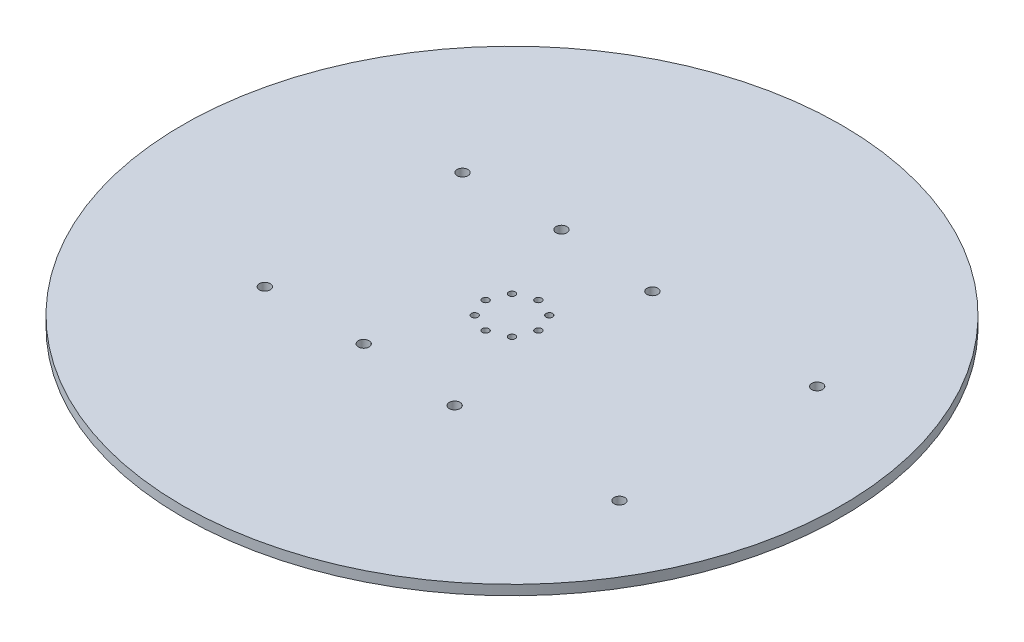
SolidWorks part; units mm, degrees
material "ABS"
ref_plane "Front Plane" through (0, 0, 0) normal (0, 0, 1) x (1, 0, 0)
ref_plane "Top Plane" through (0, 0, 0) normal (0, 1, 0) x (1, 0, 0)
ref_plane "Right Plane" through (0, 0, 0) normal (1, 0, 0) x (0, 0, -1)
sketch "Sketch2" plane through (0, 0, 0) normal (0, 1, 0) x (1, 0, 0)
  circle A0 centre (0, 0) radius 100
  dimension "D1" = 200
extrude "Boss-Extrude1" add sketch "Sketch2" along normal blind 3
sketch "Sketch3" plane through (0, 0, 0) normal (0, -1, 0) x (1, 0, 0)
  circle A0 centre (0, 75) radius 10
  dimension "D1" = 75
  dimension "D2" = 20
extrude "Boss-Extrude2" add sketch "Sketch3" along normal blind 4.75
sketch "Sketch4" plane through (0, 0, 0) normal (0, 0, 1) x (1, 0, 0)
  line L0 (0, 3) -> (0, -49997) construction
  line L1 (100, 3) -> (-100, 3) construction
  point P4 (0, 3)
pattern_circular "CirPattern1" count 5 over 360 about axis through (0, 3, 0) along (0, -1, 0) of "Boss-Extrude2"
fillet "Fillet3" radius 10 5 edges at (0, -4.75, 65) (61.8187, -4.75, 20.0861) (38.206, -4.75, -52.5861) (-38.206, -4.75, -52.5861) (-61.8187, -4.75, 20.0861)
sketch "Sketch5" plane through (0, 0, 0) normal (0, -1, 0) x (1, 0, 0)
  line L1 (-0.75, -9.5) -> (0.75, -9.5)
  line L2 (-0.75, -9.5) -> (-0.75, -12.5)
  line L3 (-0.75, -12.5) -> (0.75, -12.5)
  line L4 (0.75, -9.5) -> (0.75, -12.5)
  line L5 (-0.75, -9.5) -> (0.75, -12.5) construction
  line L6 (-0.75, -12.5) -> (0.75, -9.5) construction
  circle A0 centre (0, 0) radius 11
  circle A1 centre (0, 8) radius 1
  circle A2 centre (5.6569, 5.6569) radius 1
  circle A3 centre (8, 0) radius 1
  circle A4 centre (5.6569, -5.6569) radius 1
  circle A5 centre (0, -8) radius 1
  circle A6 centre (-5.6569, -5.6569) radius 1
  circle A7 centre (-8, 0) radius 1
  circle A8 centre (-5.6569, 5.6569) radius 1
  point P5 (0, -11)
  point P22 (0, 0)
  dimension "D1" = 22
  dimension "D2" = 2
  dimension "D3" = 8
  dimension "D5" = 8
  dimension "D6" = 1.5
  dimension "D7" = 3
  dimension "D4" = 8
extrude "Cut-Extrude1" cut sketch "Sketch5" against normal up to surface (3 mm away) contours A8 | A1 | A2 | A3 | A4 | A5 | A6 | A7 up to face at (0, 3, 100)
extrude "Boss-Extrude3" add sketch "Sketch5<3>" along normal blind 3 contours L2 A0 L4 L1 | A0 L2 L3 L4 region at (0, 0, -10.2458) region at (0, 0, -11.7457)
sketch "Sketch5<3>" plane through (0, 0, 0) normal (0, -1, 0) x (1, 0, 0) same geometry as "Sketch5"
sketch "Sketch6" plane through (0, 3, 0) normal (0, 1, 0) x (1, 0, 0)
  line L1 (-45, 30) -> (-15, 30)
  line L2 (-45, 30) -> (-45, -30)
  line L3 (-45, -30) -> (-15, -30)
  line L4 (-15, 30) -> (-15, -30)
  circle A0 centre (-45, 30) radius 2
  circle A1 centre (-15, 30) radius 2
  circle A2 centre (-15, -30) radius 2
  circle A3 centre (-45, -30) radius 2
  point P4 (-15, 0)
  dimension "D4" = 4
  dimension "D1" = 30
  dimension "D2" = 60
  dimension "D3" = 15
  dimension "D5" = 2
  dimension "D6" = 2
hole_wizard "Tap Drill for M4x0.7 Tap1" positions "3DSketch1" profile "Sketch7" hole size "M4x0.7" standard "ANSI Metric" end condition up to next
sketch3d "3DSketch1"
  point P0 (-45, 3, -30)
  point P3 (-15, 3, -30)
  point P6 (-45, 3, 30)
  point P9 (-15, 3, 30)
sketch "Sketch7" plane through (-45, 3, -30) normal (1, 0, 0) x (0, 0, 1)
  line L0 (0, 0) -> (0, 3)
  line L1 (0, 3) -> (1.65, 3)
  line L2 (1.65, 3) -> (1.65, 0)
  line L5 (1.65, 0) -> (0, 0)
  line L11 (0, -6.35) -> (0, 107.95) construction
  dimension "Thru Hole Dia." = 3.3
  dimension "Thru Hole Depth" = 3
sketch "Sketch8" plane through (0, 3, 0) normal (0, 1, 0) x (1, 0, 0)
  line L5 (-15, 30) -> (-15, -30) construction
  line L7 (15, 27.6) -> (65, 27.6)
  line L8 (15, 27.6) -> (15, -32.4)
  line L9 (15, -32.4) -> (65, -32.4)
  line L10 (65, 27.6) -> (65, -32.4)
  line L13 (-45, 30) -> (-15, 30) construction
  line L14 (13.9, -16) -> (65, -16)
  line L15 (13.9, -13.75) -> (13.9, -18.25) construction
  circle A0 centre (15, 27.6) radius 2
  circle A1 centre (65, 27.6) radius 2
  circle A2 centre (15, -32.4) radius 2
  circle A3 centre (65, -32.4) radius 2
  dimension "D4" = 4
  dimension "D5" = 4
  dimension "D6" = 4
  dimension "D7" = 4
  dimension "D1" = 50
  dimension "D2" = 60
  dimension "D3" = 30
  dimension "D8" = 2.4
  dimension "D9" = 0
hole_wizard "Tap Drill for M4x0.7 Tap2" positions "3DSketch2" profile "Sketch9" hole size "M4x0.7" standard "ANSI Metric" end condition up to next
sketch3d "3DSketch2"
  point P0 (15, 3, -27.6)
  point P3 (15, 3, 32.4)
  point P6 (65, 3, 32.4)
  point P9 (65, 3, -27.6)
sketch "Sketch9" plane through (15, 3, -27.6) normal (1, 0, 0) x (0, 0, 1)
  line L0 (0, 0) -> (0, 3)
  line L1 (0, 3) -> (1.65, 3)
  line L2 (1.65, 3) -> (1.65, 0)
  line L5 (1.65, 0) -> (0, 0)
  line L11 (0, -6.35) -> (0, 107.95) construction
  dimension "Thru Hole Dia." = 3.3
  dimension "Thru Hole Depth" = 3
